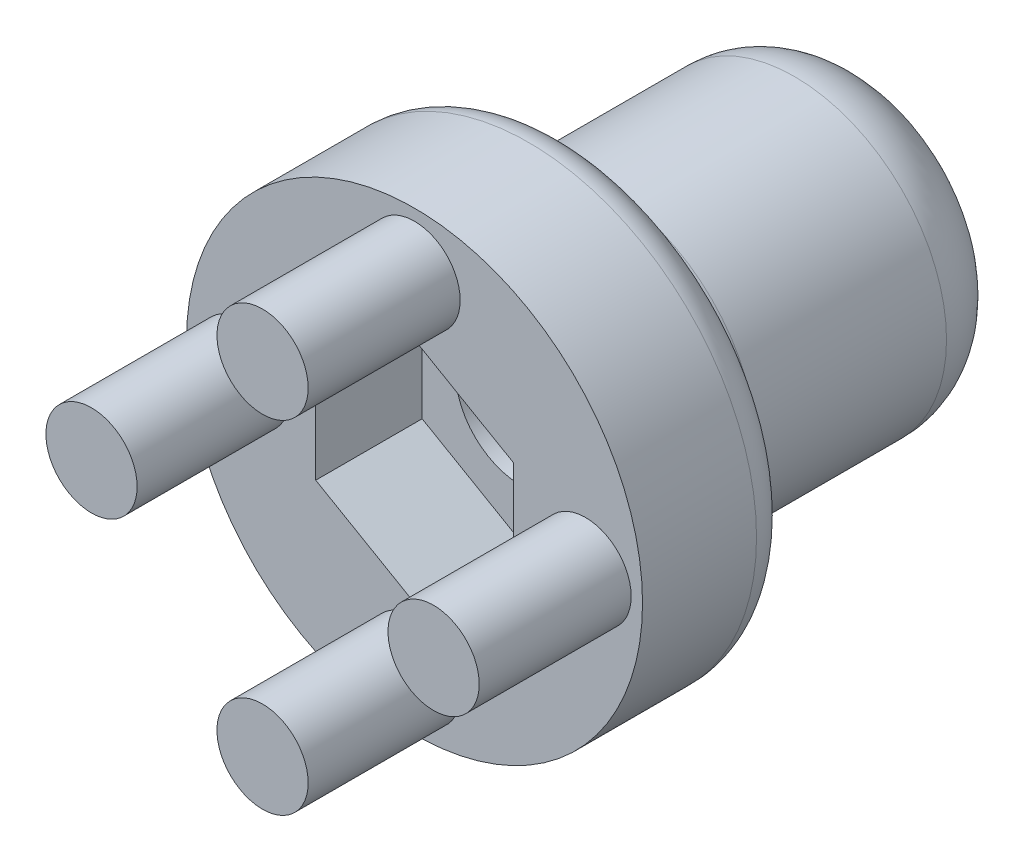
SolidWorks part; units mm, degrees
ref_plane "Front Plane" through (0, 0, 0) normal (0, 0, 1) x (1, 0, 0)
ref_plane "Top Plane" through (0, 0, 0) normal (0, 1, 0) x (1, 0, 0)
ref_plane "Right Plane" through (0, 0, 0) normal (1, 0, 0) x (0, 0, -1)
sketch "Sketch1" plane through (0, 0, 0) normal (0, 0, 1) x (1, 0, 0)
  circle A0 centre (0, 0) radius 4.3
  circle A1 centre (0, 0) radius 10
  dimension "D1" = 8.6
  dimension "D2" = 20
extrude "Boss-Extrude2" add sketch "Sketch1" along normal blind 30
sketch "Sketch2" plane through (0, 0, 30) normal (0, 0, 1) x (1, 0, 0)
  line L1 (0, 7.5056) -> (-6.5, 3.7528)
  line L2 (-6.5, 3.7528) -> (-6.5, -3.7528)
  line L3 (-6.5, -3.7528) -> (0, -7.5056)
  line L4 (0, -7.5056) -> (6.5, -3.7528)
  line L5 (6.5, -3.7528) -> (6.5, 3.7528)
  line L6 (6.5, 3.7528) -> (0, 7.5056)
  circle A0 centre (0, 0) radius 6.5 construction
  dimension "D1" = 13
extrude "Cut-Extrude1" cut sketch "Sketch2" against normal blind 7
sketch "Sketch3" plane through (0, 0, 30) normal (0, 0, 1) x (1, 0, 0)
  circle A0 centre (0, 0) radius 15
  circle A1 centre (0, 0) radius 10 construction
  circle A2 centre (0, 0) radius 10
  dimension "D1" = 30
extrude "Boss-Extrude3" add sketch "Sketch3" against normal blind 10 contours A0 | A2
fillet "Fillet1" radius 2.5 2 edges at (15, 0, 20) (10, 0, 20)
fillet "Fillet2" radius 5 1 edges at (10, 0, 0)
sketch "Sketch4" plane through (0, 0, 30) normal (0, 0, 1) x (1, 0, 0)
  line L0 (0, 15) -> (0, 7.5056)
  circle A0 centre (0, 0) radius 15 construction
  circle A1 centre (0, 11.2528) radius 3
  circle A2 centre (11.2528, 0) radius 3
  circle A3 centre (0, -11.2528) radius 3
  circle A4 centre (-11.2528, 0) radius 3
  point P16 (0, 0)
  dimension "D1" = 6
  dimension "D2" = 4
extrude "Boss-Extrude4" add sketch "Sketch4" along normal blind 10 contours A2 | L0 A1 | L0 A1 | A4 | A3 region at (1.2732, 11.2528, 30) region at (-1.2732, 11.2528, 30) region at (11.2528, 0, 30) region at (0, -11.2528, 30) region at (-11.2528, 0, 30)
